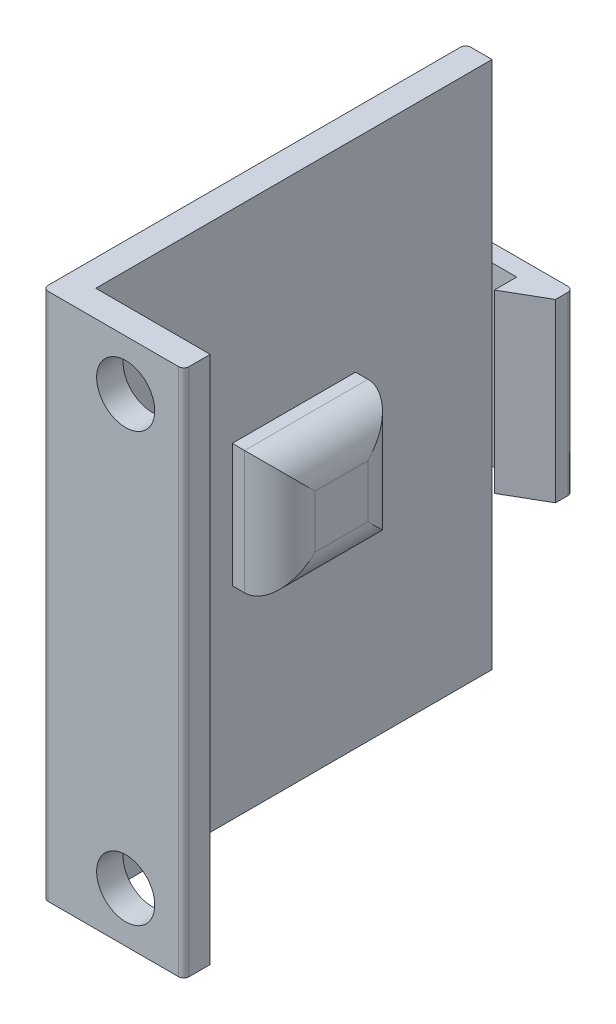
SolidWorks part; units mm, degrees
ref_plane "Front Plane" through (0, 0, 0) normal (0, 0, 1) x (1, 0, 0)
ref_plane "Top Plane" through (0, 0, 0) normal (0, 1, 0) x (1, 0, 0)
ref_plane "Right Plane" through (0, 0, 0) normal (1, 0, 0) x (0, 0, -1)
sketch "Sketch1" plane through (0, 0, 0) normal (0, 1, 0) x (1, 0, 0)
  line L0 (0, 0) -> (-2.2, 0)
  line L5 (-2.2, 0) -> (-2.2, -1.2702)
  line L6 (-2.2, -1.2702) -> (0, 0)
  dimension "D1" = 60
  dimension "D2" = 2.2
extrude "Boss-Extrude1" add sketch "Sketch1" along normal blind 5 and the other way blind 5
sketch "Sketch2" plane through (0, 0, 0) normal (0, 0, -1) x (-1, 0, 0)
  line L0 (0, 5) -> (2.2, 5) construction
  line L1 (0, -5) -> (3.6, -5)
  line L2 (0, -5) -> (0, 5)
  line L3 (0, 5) -> (3.6, 5)
  line L4 (3.6, -5) -> (3.6, 5)
  line L5 (0, -5) -> (3.6, 5) construction
  line L6 (0, 5) -> (3.6, -5) construction
  line L7 (2.2, -5) -> (2.2, 5) construction
  point P4 (1.8, 0)
  dimension "D1" = 1.4
extrude "Boss-Extrude2" add sketch "Sketch2" along normal blind 1
sketch "Sketch3" plane through (-3.6, 0, 0) normal (-1, 0, 0) x (0, 0, 1)
  line L0 (0, 0) -> (12.5427, 0) construction
  line L1 (0, -15) -> (22.5, -15)
  line L2 (0, -15) -> (0, 15)
  line L3 (0, 15) -> (22.5, 15)
  line L4 (22.5, -15) -> (22.5, 15)
  line L5 (0, -15) -> (22.5, 15) construction
  line L6 (0, 15) -> (22.5, -15) construction
  line L7 (0, -5) -> (0, 5) construction
  line L9 (0, 5) -> (-1, 5)
  line L10 (0, 5) -> (0, -5)
  line L11 (0, -5) -> (-1, -5)
  line L12 (-1, 5) -> (-1, -5)
  line L13 (0, 5) -> (-1, -5) construction
  line L14 (0, -5) -> (-1, 5) construction
  point P4 (11.25, 0)
  point P16 (-0.5, 0)
  line M6 (0, -5) -> (0, 5)
  line M7 (0, 5) -> (-1, 5)
  line M8 (-1, 5) -> (-1, -5)
  line M9 (-1, -5) -> (0, -5)
  dimension "D1" = 22.5
  dimension "D2" = 30
extrude "Boss-Extrude3" add sketch "Sketch3" along normal blind 1.5 contours L1 L4 L3 L2 M6 | M9 M6 M7 M8 region at (-3.6, 0, 11.25) region at (-3.6, 0, -0.5)
sketch "Sketch4" plane through (0, 0, 22.5) normal (0, 0, 1) x (1, 0, 0)
  line L0 (-4.35, 0) -> (3.106, 0) construction
  line L1 (-5.1, -15) -> (-3.6, -15)
  line L2 (-5.1, -15) -> (-5.1, 15)
  line L3 (-5.1, 15) -> (-3.6, 15)
  line L4 (-3.6, -15) -> (-3.6, 15)
  line L5 (-5.1, -15) -> (-3.6, 15) construction
  line L6 (-5.1, 15) -> (-3.6, -15) construction
  line L7 (-3.6, -15) -> (2.9, -15)
  line L8 (-3.6, -15) -> (-3.6, 15)
  line L9 (-3.6, 15) -> (2.9, 15)
  line L10 (2.9, -15) -> (2.9, 15)
  line L11 (-3.6, -15) -> (2.9, 15) construction
  line L12 (-3.6, 15) -> (2.9, -15) construction
  circle A0 centre (-0.4, 12.15) radius 1.65
  circle A1 centre (-0.4, -12.15) radius 1.65
  point P4 (-4.35, 0)
  point P11 (-0.35, 0)
  line M5 (-3.6, -15) -> (-3.6, 15)
  line M6 (-3.6, 15) -> (-5.1, 15)
  line M7 (-5.1, 15) -> (-5.1, -15)
  line M8 (-5.1, -15) -> (-3.6, -15)
  dimension "D4" = 3.3
  dimension "D1" = 30
  dimension "D2" = 6.5
  dimension "D3" = 3.3
  dimension "D5" = 2.85
extrude "Boss-Extrude4" add sketch "Sketch4" along normal blind 1.5 contours L7 L10 L9 M5 | M8 M5 M6 M7 region at (-4.35, 0, 22.5) region at (-0.3452, 0, 22.5)
ref_plane "Plane1" through (0, 0, 0) normal (0, 1, 0) x (1, 0, 0)
fillet "Fillet1" radius 0.3 6 edges at (-5.1, 0, -1) (-5.1, 0, 24) (-5.1, -10, 0) (-5.1, 10, 0) (2.9, 0, 24) (0, 0, -1)
sketch "Sketch5" plane through (-3.6, 0, 0) normal (1, 0, 0) x (0, 0, -1)
  line L0 (0, -15) -> (-22.5, -15) construction
  line L1 (0, 15) -> (-22.5, 15)
  line L2 (0, 15) -> (0, -15)
  line L3 (0, -15) -> (-22.5, -15)
  line L4 (-22.5, 15) -> (-22.5, -15)
  line L5 (0, 15) -> (-22.5, -15) construction
  line L6 (0, -15) -> (-22.5, 15) construction
  line L7 (-14.75, 3.5) -> (-7.75, 3.5)
  line L8 (-14.75, 3.5) -> (-14.75, -3.5)
  line L9 (-14.75, -3.5) -> (-7.75, -3.5)
  line L10 (-7.75, 3.5) -> (-7.75, -3.5)
  line L11 (-14.75, 3.5) -> (-7.75, -3.5) construction
  line L12 (-14.75, -3.5) -> (-7.75, 3.5) construction
  line L16 (-22.5, -15) -> (-22.5, 15) construction
  point P4 (-11.25, 0)
  point P7 (-11.25, 0)
  dimension "D1" = 7
  dimension "D2" = 7
extrude "Boss-Extrude5" add sketch "Sketch5" along normal blind 2.7 contours L8 L7 L10 L9
fillet "Fillet2" radius 2 4 edges at (-0.9, 0, 14.75) (-0.9, 3.5, 11.25) (-0.9, 0, 7.75) (-0.9, -3.5, 11.25)
equation "\"WallThick\"= 1.2'thickness of wall for printer"
equation "\"dHole\"= 3.3'diameter of screw hole"
